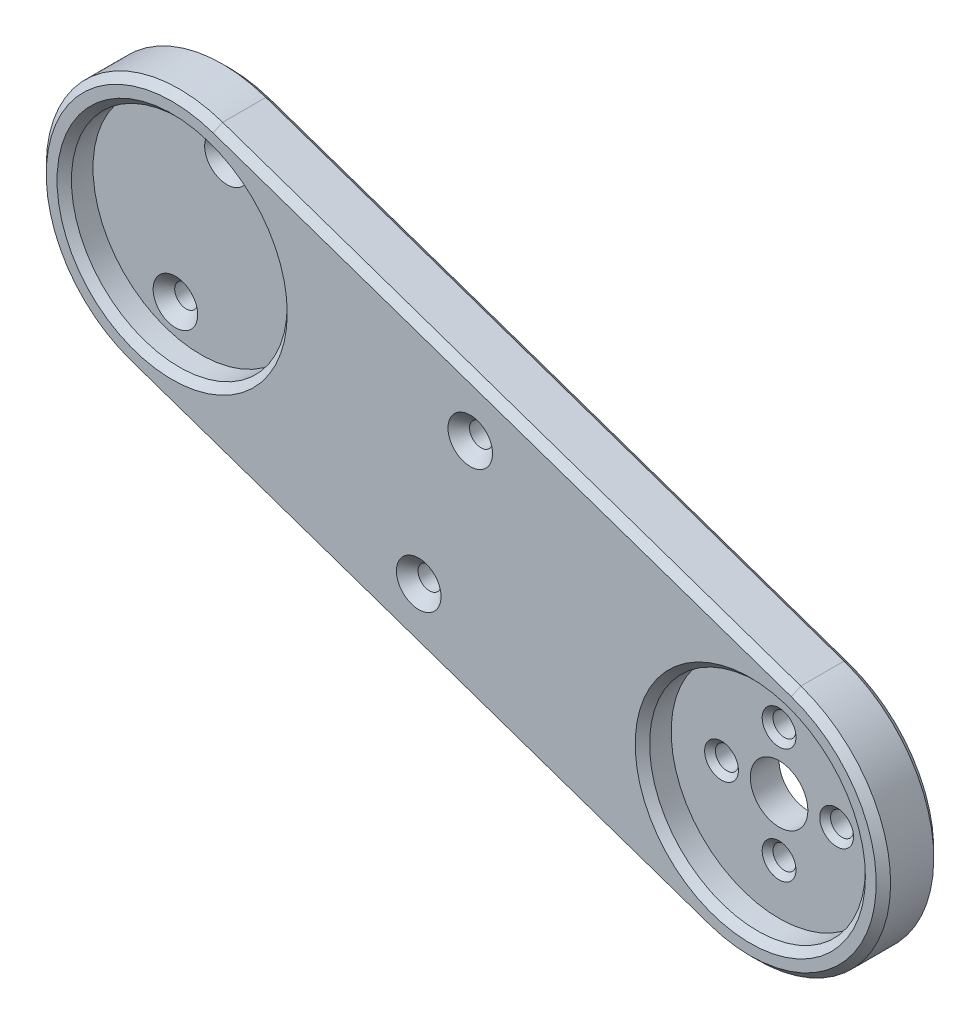
SolidWorks part; units mm, degrees
ref_plane "Front Plane" through (0, 0, 0) normal (0, 0, 1) x (1, 0, 0)
ref_plane "Top Plane" through (0, 0, 0) normal (0, 1, 0) x (1, 0, 0)
ref_plane "Right Plane" through (0, 0, 0) normal (1, 0, 0) x (0, 0, -1)
sketch "Sketch1" plane through (0, 0, 0) normal (0, 0, 1) x (1, 0, 0)
  line L0 (2.2422, 2.1423) -> (2.2422, 10.1423) construction
  line L1 (2.2422, 2.1423) -> (2.2422, -5.8577) construction
  line L2 (2.2422, 2.1423) -> (10.2422, 2.1423) construction
  line L3 (2.2422, 2.1423) -> (-5.7578, 2.1423) construction
  line L4 (-84.1491, 12.3302) -> (-3.7821, -15.3493)
  line L5 (-72.1003, 47.3135) -> (8.2666, 19.6339)
  arc A0 (-72.1003, 47.3135) -> (-84.1491, 12.3302) centre (-78.1247, 29.8218) ccw
  arc A1 (-3.7821, -15.3493) -> (8.2666, 19.6339) centre (2.2422, 2.1423) ccw
  circle A4 centre (2.2422, 10.1423) radius 1.6
  circle A5 centre (-5.7578, 2.1423) radius 1.6
  circle A7 centre (10.2422, 2.1423) radius 1.6
  circle A8 centre (2.2422, -5.8577) radius 1.6
  circle A9 centre (2.2422, 2.1423) radius 18.5 construction
  circle A10 centre (2.2422, 2.1423) radius 15
  circle A11 centre (-78.1247, 29.8218) radius 15
  dimension "D1" = 37
  dimension "D2" = 37
  dimension "D3" = 85
  dimension "D4" = 30
  dimension "D6" = 8
  dimension "D9" = 3.2
  dimension "D10" = 30
  dimension "D5" = 8
  dimension "D7" = 8
  dimension "D8" = 8
extrude "Boss-Extrude1" add sketch "Sketch1" along normal blind 8 contours A1 L5 A0 L4 region at (-37.9412, 15.9821, 0)
extrude "Boss-Extrude4" add sketch "Sketch1<5>" along normal blind 4 contours A10 A4 A5 A7 A8 | A11 region at (2.2422, 2.1423, 0) region at (-78.1247, 29.8218, 0)
sketch "Sketch1<5>" plane through (0, 0, 0) normal (0, 0, 1) x (1, 0, 0) same geometry as "Sketch1"
chamfer "Chamfer1" distance 0.75 angle 45 4 edges at (-4.1578, 2.1423, 4) (3.8422, -5.8577, 4) (11.8422, 2.1423, 4) (3.8422, 10.1423, 4)
chamfer "Chamfer3" distance 1 angle 45 2 edges at (17.2422, 2.1423, 8) (-63.1247, 29.8218, 8)
sketch "Sketch8" plane through (0, 0, 0) normal (0, 0, -1) x (-1, 0, 0)
  line L0 (-2.2422, 10.1423) -> (-2.2422, -5.8577) construction
  circle A0 centre (-2.2422, 2.1423) radius 4
  dimension "D1" = 8
extrude "Cut-Extrude1" cut sketch "Sketch8" against normal through all both and the other way through all
sketch "Sketch10" plane through (0, 0, 0) normal (0, 0, -1) x (-1, 0, 0)
  line L0 (76.3314, 43.9584) -> (85.4168, 17.5791)
  line L4 (76.3314, 43.9584) -> (32.9332, 29.0114)
  line L5 (85.4168, 17.5791) -> (42.0186, 2.6322)
  line L6 (32.9332, 29.0114) -> (42.0186, 2.6322)
  line L7 (72.1003, 47.3135) -> (-8.2666, 19.6339) construction
  line L8 (77.292, 41.1692) -> (74.5028, 40.2085) construction
  line L9 (74.5028, 40.2085) -> (73.5421, 42.9977) construction
  line L10 (54.6323, 36.4849) -> (63.7177, 10.1056) construction
  line L11 (59.175, 23.2953) -> (37.4759, 15.8218) construction
  circle A2 centre (74.5028, 40.2085) radius 1.6
  circle A3 centre (36.6831, 27.1829) radius 1.6
  circle A4 centre (81.6669, 19.4077) radius 1.6
  circle A5 centre (43.8472, 6.382) radius 1.6
  dimension "D4" = 45.9
  dimension "D1" = 27.9
  dimension "D2" = 2.95
  dimension "D3" = 2.95
extrude "Cut-Extrude2" cut sketch "Sketch10" against normal through all both and the other way through all contours A3 | A2 | A4 | A5 region at (-74.5028, 40.2085, 0) region at (-36.6831, 27.1829, 0) region at (-81.6669, 19.4077, 0) region at (-43.8472, 6.382, 0)
chamfer "Chamfer4" distance 1.5 angle 45 4 edges at (-72.9028, 40.2085, 4) (-45.4472, 6.382, 8) (-38.2831, 27.1829, 8) (-80.0669, 19.4077, 4)
chamfer "Chamfer5" distance 1 angle 45 4 edges at (-31.9169, 33.4737, 0) (-95.6163, 35.8462, 0) (19.7339, -3.8821, 0) (-43.9656, -1.5096, 0)
chamfer "Chamfer6" distance 1 angle 45 4 edges at (-31.9169, 33.4737, 8) (-95.6163, 35.8462, 8) (19.7339, -3.8821, 8) (-43.9656, -1.5096, 8)
